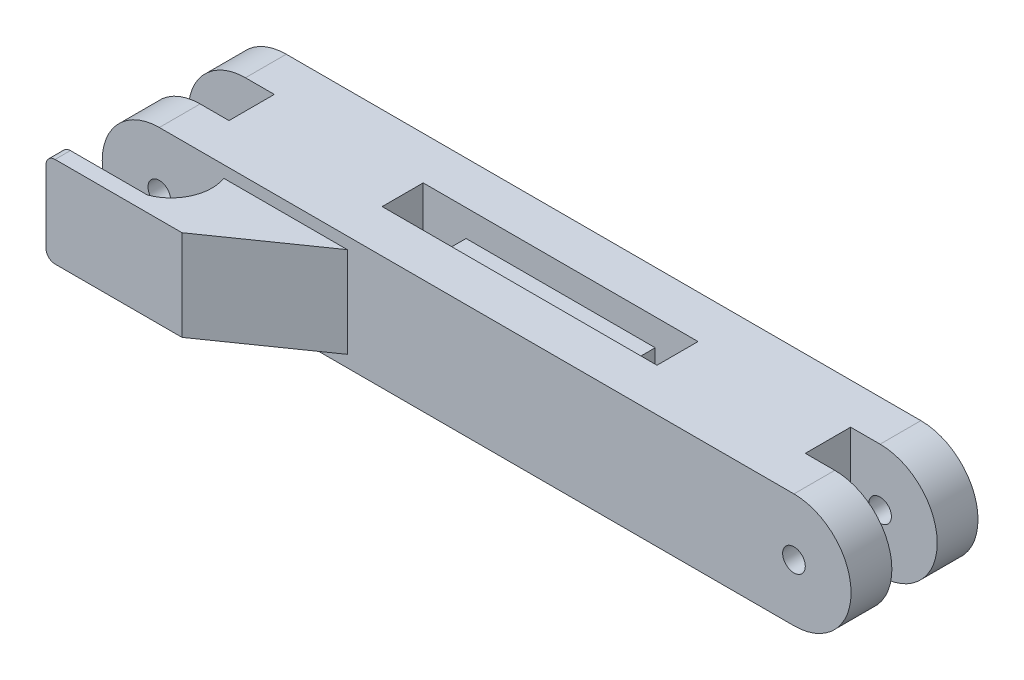
SolidWorks part; units mm, degrees
ref_plane "Front" through (0, 0, 0) normal (0, 0, 1) x (1, 0, 0)
ref_plane "Top" through (0, 0, 0) normal (0, 1, 0) x (1, 0, 0)
ref_plane "Right" through (0, 0, 0) normal (1, 0, 0) x (0, 0, -1)
sketch "Sketch1" plane through (0, 0, 0) normal (0, 0, 1) x (1, 0, 0)
  line L0 (-47.2174, -8.0761) -> (130.5826, -8.0761) construction
  line L1 (-47.2174, 7.9239) -> (130.5826, 7.9239)
  line L2 (-47.2174, -24.0761) -> (130.5826, -24.0761)
  arc A0 (-47.2174, 7.9239) -> (-47.2174, -24.0761) centre (-47.2174, -8.0761) ccw
  arc A1 (130.5826, -24.0761) -> (130.5826, 7.9239) centre (130.5826, -8.0761) ccw
  circle A2 centre (-47.2174, -8.0761) radius 3.175
  circle A3 centre (130.5826, -8.0761) radius 3.175
  point P2 (41.6826, -8.0761)
  dimension "D1" = 16
  dimension "D3" = 6.35
  dimension "D4" = 6.35
  dimension "D2" = 177.8
extrude "Boss-Extrude1" add sketch "Sketch1" along normal blind 11.43
sketch "Sketch2" plane through (0, 0, 11.43) normal (0, 0, 1) x (1, 0, 0)
  line L2 (-39.1367, -24.0761) -> (-39.1367, 7.9239)
  line L4 (130.5826, 7.9239) -> (-47.2174, 7.9239) construction
  line L7 (-47.2174, -24.0761) -> (130.5826, -24.0761) construction
  line L9 (122.3276, -24.0761) -> (122.3276, 7.9239)
  line L10 (-39.1367, 7.9239) -> (122.3276, 7.9239)
  line L11 (-39.1367, -24.0761) -> (122.3276, -24.0761)
  point P13 (-39.1367, -8.0761)
  point P16 (16.9972, 0.4239)
  point P24 (122.3276, -8.0761)
extrude "Boss-Extrude2" add sketch "Sketch2" along normal blind 12.7
sketch "Sketch5" plane through (0, 0, 24.13) normal (0, 0, 1) x (1, 0, 0)
  line L0 (-47.2174, -8.0761) -> (130.5826, -8.0761) construction
  line L1 (-47.2174, 7.9239) -> (130.5826, 7.9239)
  line L2 (-47.2174, -24.0761) -> (130.5826, -24.0761)
  arc A0 (-47.2174, 7.9239) -> (-47.2174, -24.0761) centre (-47.2174, -8.0761) ccw
  arc A1 (130.5826, -24.0761) -> (130.5826, 7.9239) centre (130.5826, -8.0761) ccw
  circle A2 centre (-47.2174, -8.0761) radius 3.175
  circle A3 centre (130.5826, -8.0761) radius 3.175
  point P4 (41.6826, -8.0761)
  dimension "D1" = 16
  dimension "D2" = 6.35
  dimension "D3" = 6.35
extrude "Boss-Extrude3" add sketch "Sketch5" along normal blind 11.43
sketch "Sketch6" plane through (0, 7.9239, 0) normal (0, 1, 0) x (1, 0, 0)
  line L0 (41.6826, 0) -> (41.6826, -35.56)
  line L1 (130.5826, 0) -> (-47.2174, 0) construction
  line L2 (130.5826, -35.56) -> (-47.2174, -35.56) construction
  line L3 (-39.1367, -17.78) -> (122.3276, -17.78)
  line L4 (-39.1367, -24.13) -> (-39.1367, -11.43) construction
  line L5 (122.3276, -24.13) -> (122.3276, -11.43) construction
  line L7 (3.1826, -23.53) -> (80.1826, -23.53)
  line L8 (3.1826, -23.53) -> (3.1826, -12.03)
  line L9 (3.1826, -12.03) -> (80.1826, -12.03)
  line L10 (80.1826, -23.53) -> (80.1826, -12.03)
  line L11 (3.1826, -23.53) -> (80.1826, -12.03) construction
  line L12 (3.1826, -12.03) -> (80.1826, -23.53) construction
  point P12 (41.6826, -17.78)
extrude "Cut-Extrude1" cut sketch "Sketch6" against normal blind 7.5 contours L7 L10 L9 L8
sketch "Sketch7" plane through (0, 0.4239, 0) normal (0, 1, 0) x (1, 0, 0)
  line L5 (3.1826, -23.53) -> (80.1826, -23.53) construction
  line L10 (3.1826, -12.03) -> (15.1826, -12.03)
  line L11 (3.1826, -12.03) -> (3.1826, -23.53)
  line L12 (3.1826, -23.53) -> (15.1826, -23.53)
  line L13 (15.1826, -12.03) -> (15.1826, -23.53)
  line L14 (3.1826, -12.03) -> (80.1826, -12.03) construction
  line L15 (80.1826, -23.53) -> (68.1826, -23.53)
  line L16 (80.1826, -23.53) -> (80.1826, -12.03)
  line L17 (80.1826, -12.03) -> (68.1826, -12.03)
  line L18 (68.1826, -23.53) -> (68.1826, -12.03)
sketch "Sketch10" plane through (0, 0, 35.56) normal (0, 0, 1) x (1, 0, 0)
  line L0 (-47.2174, -24.0761) -> (130.5826, -24.0761) construction
  line L1 (-34.5174, -20.7761) -> (-57.3774, -20.7761)
  line L3 (-34.5174, 4.6239) -> (-57.3774, 4.6239)
  line L4 (-59.9174, -18.2361) -> (-59.9174, 2.0839)
  line L5 (-34.5174, -20.7761) -> (-59.9174, 4.6239) construction
  line L6 (-34.5174, 4.6239) -> (-59.9174, -20.7761) construction
  line L7 (-34.5174, 4.6239) -> (-21.8174, 4.6239)
  line L9 (-34.5174, -20.7761) -> (-21.8174, -20.7761)
  line L10 (-21.8174, 4.6239) -> (-21.8174, -20.7761)
  arc A1 (-57.3774, -20.7761) -> (-59.9174, -18.2361) centre (-57.3774, -18.2361) cw
  arc A2 (-57.3774, 4.6239) -> (-59.9174, 2.0839) centre (-57.3774, 2.0839) ccw
  dimension "D1" = 2.54
  dimension "D2" = 35.56
  dimension "D3" = 25.4
  dimension "D4" = 12.7
  dimension "D5" = 3.3
extrude "Boss-Extrude4" add sketch "Sketch10" along normal blind 19.05 contours L4 A2 L3 L7 L10 L9 L1 A1
sketch "Sketch14" plane through (0, 4.6239, 0) normal (0, 1, 0) x (1, 0, 0)
  line L0 (-59.9174, -35.56) -> (-29.1834, -35.56)
  line L1 (-56.9493, -35.56) -> (-21.8174, -35.56) construction
  line L2 (-59.9174, -35.56) -> (-59.9174, -50.3102)
  line L3 (-59.9174, -54.61) -> (-59.9174, -35.56) construction
  line L4 (-59.9174, -50.3102) -> (-35.7956, -50.3102)
  arc A0 (-29.1834, -35.56) -> (-35.7956, -50.3102) centre (-39.8646, -39.629) cw
  dimension "D1" = 11.43
  dimension "D2" = 24.1218
  dimension "D3" = 14.7502
  dimension "D4" = 30.734
extrude "Cut-Extrude3" cut sketch "Sketch14" against normal blind 30.48
sketch "Sketch15" plane through (0, -20.7761, 0) normal (0, -1, 0) x (1, 0, 0)
  line L0 (-21.8174, 35.56) -> (5.4637, 35.56)
  line L1 (-47.2174, 35.56) -> (130.5826, 35.56) construction
  line L2 (-21.8174, 54.61) -> (5.4637, 35.56)
  line L3 (-21.8174, 54.61) -> (-21.8174, 35.56)
extrude "Boss-Extrude5" add sketch "Sketch15" against normal blind 25.4
extrude "Cut-Extrude4" cut sketch "Sketch7" against normal blind 50.8 contours L18 L17 L16 L15
extrude "Cut-Extrude5" cut sketch "Sketch7<5>" against normal blind 50.8 contours L13 L12 L11 L10
sketch "Sketch7<5>" plane through (0, 0.4239, 0) normal (0, 1, 0) x (1, 0, 0) same geometry as "Sketch7"
